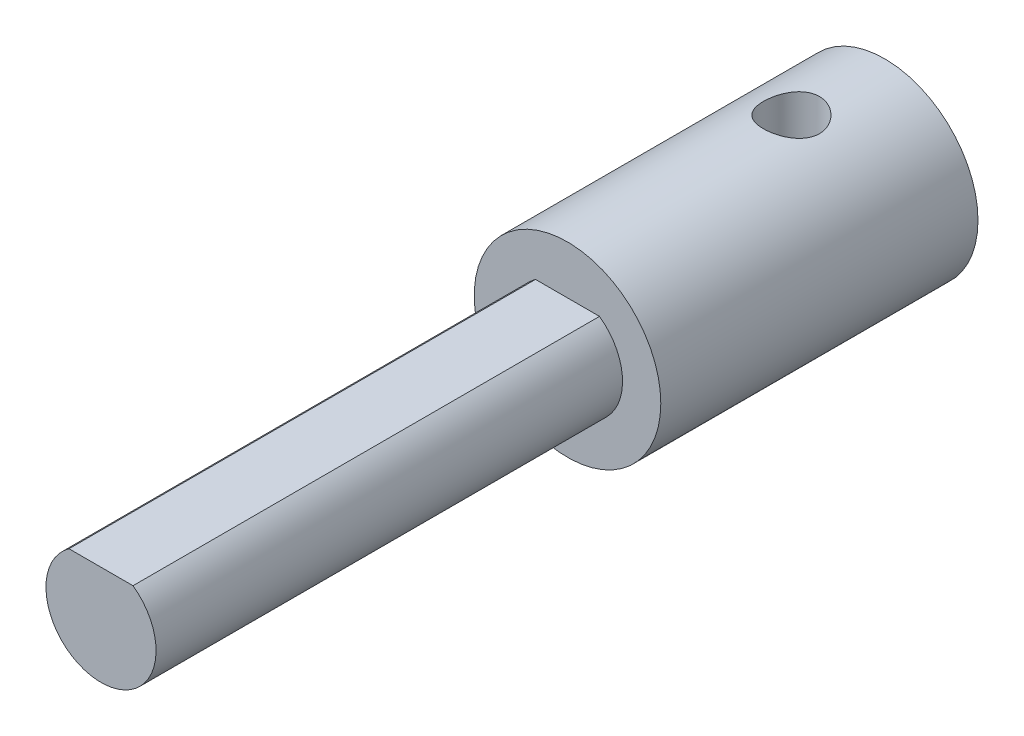
SolidWorks part; units mm, degrees
ref_plane "Front" through (0, 0, 0) normal (0, 0, 1) x (1, 0, 0)
ref_plane "Top" through (0, 0, 0) normal (0, 1, 0) x (1, 0, 0)
ref_plane "Right" through (0, 0, 0) normal (1, 0, 0) x (0, 0, -1)
sketch "Sketch1" plane through (0, 0, 0) normal (0, 0, 1) x (1, 0, 0)
  line L0 (-1.6562, 2.65) -> (1.6562, 2.65)
  line L1 (0, 0) -> (0, 2.65) construction
  line L2 (0, 2.65) -> (0, 3.125) construction
  circle A0 centre (0, 0) radius 3.125
  circle A1 centre (0, 0) radius 5
  dimension "D1" = 6.25
  dimension "D3" = 10
  dimension "D2" = 2.65
extrude "Boss-Extrude1" add sketch "Sketch1" along normal blind 15 contours A1 A0 | L0 A0 region at (0, 2.8413, 0) region at (-4.8586, 0, 0)
sketch "Sketch3" plane through (0, 0, 0) normal (0, 1, 0) x (1, 0, 0)
  circle A0 centre (0, -5) radius 1.5
  dimension "D1" = 3
  dimension "D2" = 5
extrude "Cut-Extrude1" cut sketch "Sketch3" along normal up to next
sketch "Sketch4" plane through (0, 0, 15) normal (0, 0, 1) x (1, 0, 0)
  circle A0 centre (0, 0) radius 5
  circle A1 centre (0, 0) radius 5 construction
extrude "Boss-Extrude2" add sketch "Sketch4" along normal blind 2
sketch "Sketch6" plane through (0, 0, 17) normal (0, 0, 1) x (1, 0, 0)
  line L0 (-1.7154, 2.4) -> (1.7154, 2.4)
  circle A0 centre (0, 0) radius 2.95
  dimension "D1" = 5.9
  dimension "D2" = 2.4
extrude "Boss-Extrude3" add sketch "Sketch6" along normal blind 25 contours L0 A0 region at (0, -0.1291, 17)
